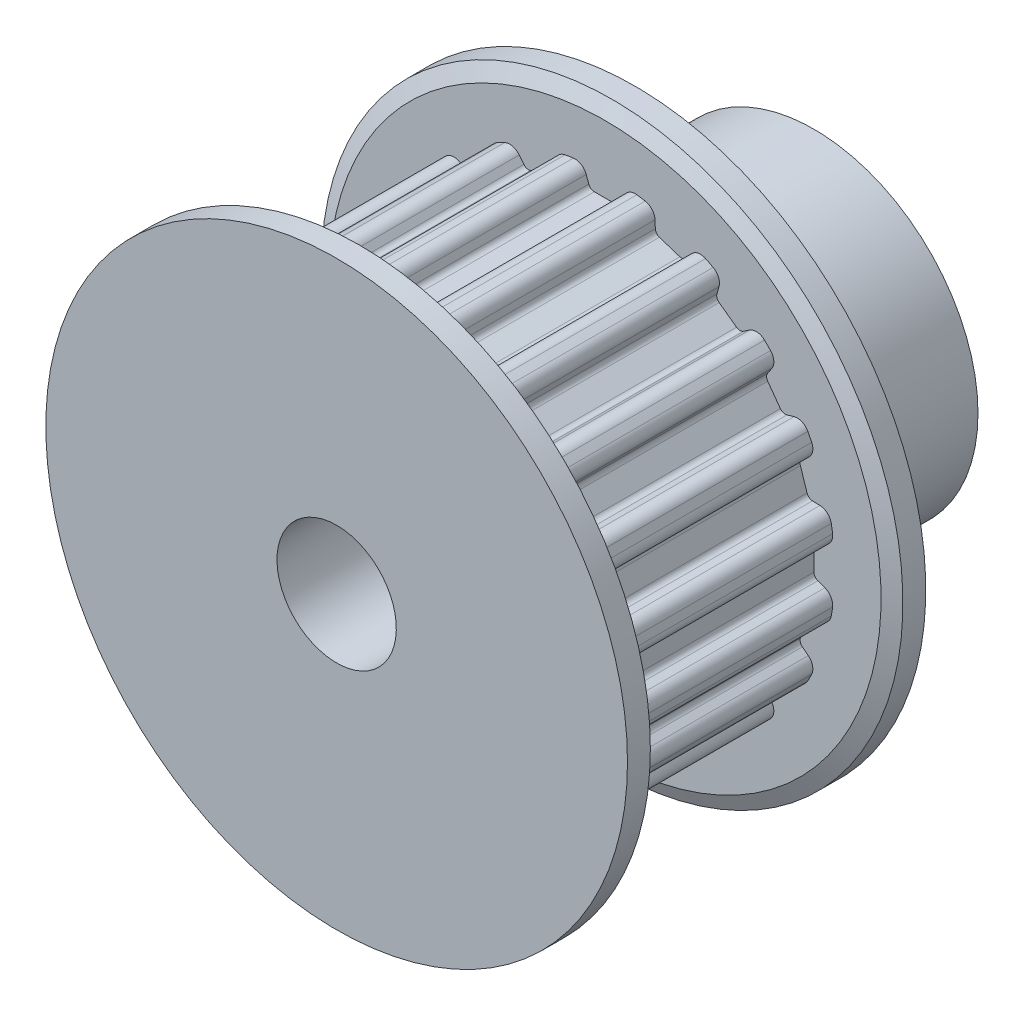
SolidWorks part; units mm, degrees
ref_plane "Front" through (0, 0, 0) normal (0, 0, 1) x (1, 0, 0)
ref_plane "Top" through (0, 0, 0) normal (0, 1, 0) x (1, 0, 0)
ref_plane "Right" through (0, 0, 0) normal (1, 0, 0) x (0, 0, -1)
sketch "support-front-body" plane through (0, 0, 0) normal (0, 0, 1) x (1, 0, 0)
  line L0 (0, 0) -> (0, 7.7) construction
  line L1 (0, 0) -> (0, -7.7) construction
  line L2 (0, 0) -> (7.7, 0) construction
  line L3 (0, 0) -> (-7.7, 0) construction
  circle A0 centre (0, 0) radius 7.7
  dimension "diam-outer" = 15.4
sketch "support-right-body" plane through (0, 0, 0) normal (1, 0, 0) x (0, 0, -1)
  line L0 (0, 0) -> (10, 0) construction
  line L1 (0, 7.7) -> (10, 7.7)
  line L2 (0, 7.7) -> (0, -7.7)
  line L3 (0, -7.7) -> (10, -7.7)
  line L4 (10, 7.7) -> (10, -7.7)
  dimension "length" = 10
sketch "support-right-chamfer" plane through (0, 0, 0) normal (1, 0, 0) x (0, 0, -1)
  line L0 (0, 0) -> (10, 0) construction
  line L1 (0, -7.7) -> (0, -6.7)
  line L2 (0, 7.7) -> (0, -7.7) construction
  line L4 (0, -6.7) -> (1, -7.7)
  line L5 (0, -7.7) -> (10, -7.7) construction
  line L7 (1, -7.7) -> (0, -7.7)
  line L9 (10, -7.7) -> (9, -7.7)
  line L11 (9, -7.7) -> (10, -6.7)
  line L12 (10, 7.7) -> (10, -7.7) construction
  line L14 (10, -6.7) -> (10, -7.7)
  dimension "height-chamfer-front" = 1
  dimension "angle-chamfer-front" = 45
  dimension "angle-chamfer-back" = 45
  dimension "height-chamfer-back" = 1
sketch "support-right-hub" plane through (0, 0, 0) normal (1, 0, 0) x (0, 0, -1)
  line L0 (16, 0) -> (10, 0) construction
  line L1 (10, 5.5) -> (16, 5.5)
  line L2 (10, 5.5) -> (10, -5.5)
  line L3 (10, -5.5) -> (16, -5.5)
  line L4 (16, 5.5) -> (16, -5.5)
  line L6 (0, 0) -> (10, 0) construction
  line L8 (0, 7.7) -> (0, -7.7) construction
  dimension "diam-hub" = 11
  dimension "length-hub" = 6
  dimension "dist-hub" = 10
sketch "support-right-bore" plane through (0, 0, 0) normal (1, 0, 0) x (0, 0, -1)
  line L0 (0, 7.7) -> (0, -7.7) construction
  line L1 (0, 2) -> (16, 2)
  line L2 (0, 2) -> (0, -2)
  line L3 (0, -2) -> (16, -2)
  line L4 (16, 2) -> (16, 0)
  line L5 (16, 0) -> (0, 0) construction
  line L6 (0, 0) -> (10, 0) construction
  line L7 (16, 0) -> (16, -2)
  line L8 (16, -2) -> (16, 2) construction
  dimension "diam-bore" = 4
  dimension "length-bore" = 16
  dimension "angle-bore-bottom" = 180
  dimension "angle-bore" = 90
sketch "support-stop-screw-hole" plane through (0, 0, 0) normal (1, 0, 0) x (0, 0, -1)
  line L1 (6.5667, 11) -> (9.4333, 11)
  line L2 (6.5667, 11) -> (6.5667, -1)
  line L3 (8, -1) -> (9.4333, -1)
  line L4 (9.4333, 11) -> (9.4333, -1)
  line L5 (8, -1) -> (8, 11) construction
  line L6 (8, -1) -> (6.5667, -1)
  line L7 (0, 0) -> (8, 0) construction
  line L8 (0, 7.7) -> (0, -7.7) construction
  dimension "diam-stop-screw-hole" = 2.8665
  dimension "dist-stop-screw-hole" = 8
  dimension "depth-stop-screw-hole" = 12
  dimension "angle-stop-screw-hole" = 180
  dimension "height-stop-screw-hole" = 11
sketch "support-front-keygroove" plane through (0, 0, 0) normal (0, 0, 1) x (1, 0, 0)
  line L0 (0, 0) -> (0, -2) construction
  line L1 (-1, 6) -> (1, 6)
  line L2 (-1, 6) -> (-1, 3.8)
  line L3 (-1, 3.8) -> (1, 3.8)
  line L4 (1, 6) -> (1, 3.8)
  line L5 (0, 0) -> (0, 2) construction
  circle A0 centre (0, 0) radius 2 construction
  dimension "width-keygroove" = 2
  dimension "dist-keygroove" = 8
  dimension "height-keygroove" = 2.2
sketch "support-front-tooth" plane through (0, 0, 0) normal (0, 0, 1) x (1, 0, 0)
  line L0 (0.5479, 7.1316) -> (0.6335, 7.3667)
  line L1 (0, 0) -> (0, 7.7) construction
  line L2 (-0.5479, 7.1316) -> (-0.6335, 7.3667)
  line L3 (-0.36, 7) -> (0.36, 7)
  line L4 (0, 7) -> (-1.0646, 7.626) construction
  line L5 (0, 7) -> (-0.5479, 7.1316) construction
  line L6 (0, 7.7) -> (0.5704, 7.6062) construction
  line L7 (0, 7.7) -> (2.4668, 7.2942) construction
  line L8 (0, 7.626) -> (0, 7) construction
  line L9 (1.0646, 7.626) -> (-1.0646, 7.626) construction
  line L10 (0, 7.626) -> (0, 8.2521) construction
  line L11 (0, 0) -> (1.2334, 7.4971) construction
  line L12 (1.4346, 7.5652) -> (1.6352, 8.1582)
  line L13 (1.6352, 8.1582) -> (3.6522, 7.4761)
  line L14 (3.6522, 7.4761) -> (3.4517, 6.883)
  line L15 (2.5836, 6.5157) -> (2.9601, 6.7755)
  line L16 (2.5836, 6.5157) -> (1.9016, 6.7464)
  line L17 (1.0646, 7.626) -> (1.0646, 8.2521)
  line L21 (-1.0646, 8.2521) -> (-1.0646, 7.626)
  line L22 (1.0646, 8.2521) -> (-1.0646, 8.2521)
  line L23 (1.9016, 6.7464) -> (1.76, 7.1814)
  line L24 (1.4346, 7.5652) -> (1.0646, 7.626) construction
  line L25 (-0.5479, 7.1316) -> (-0.5, 7) construction
  line L26 (-0.5, 7) -> (0.5, 7) construction
  line L27 (0.5, 7) -> (0.5479, 7.1316) construction
  line L28 (0.5704, 7.6062) -> (1.0093, 7.2299) construction
  arc A0 (-0.5479, 7.1316) -> (-0.36, 7) centre (-0.36, 7.2) ccw
  circle A1 centre (0, 0) radius 7.7 construction
  arc A2 (0.6335, 7.3667) -> (1.0646, 7.626) centre (1.0093, 7.2299) cw
  arc A3 (-0.6335, 7.3667) -> (-1.0646, 7.626) centre (-1.0093, 7.2299) ccw
  arc A4 (0.5479, 7.1316) -> (0.36, 7) centre (0.36, 7.2) cw
  circle A5 centre (0, 0) radius 7.7 construction
  arc A6 (1.76, 7.1814) -> (1.4346, 7.5652) centre (1.3601, 7.1722) ccw
  arc A7 (2.9601, 6.7755) -> (3.4517, 6.883) centre (3.2724, 6.5255) cw
  dimension "D3" = 0.4
  dimension "D2" = 40
  dimension "D1" = 0.2
  dimension "D4" = 1
  dimension "height-tooth" = 0.7
  dimension "pitch" = 2.5
sketch "support-right-flange" plane through (0, 0, 0) normal (1, 0, 0) x (0, 0, -1)
  line L0 (0, 4.85) -> (0, 8.1167)
  line L1 (10, 7.7) -> (10, -7.7) construction
  line L2 (0, 8.1167) -> (1, 8.1167) construction
  line L3 (1, 8.1167) -> (1, 9.75)
  line L4 (0, 9.75) -> (1, 9.75)
  line L5 (1, 8.1167) -> (1, 4.85)
  line L6 (1, 4.85) -> (0, 4.85)
  line L7 (5, 7.7) -> (5, 0) construction
  line L8 (0, 7.7) -> (10, 7.7) construction
  line L9 (0, 8.1167) -> (0, 9.75)
  line L10 (9, 4.85) -> (10, 4.85)
  line L11 (9, 8.1167) -> (9, 4.85)
  line L12 (10, 9.75) -> (9, 9.75)
  line L13 (9, 8.1167) -> (9, 9.75)
  line L14 (10, 8.1167) -> (10, 9.75)
  line L15 (10, 4.85) -> (10, 8.1167)
  line L16 (10, 0) -> (0, 0) construction
  line L17 (10, -4.85) -> (10, -8.1167)
  line L18 (10, -8.1167) -> (10, -9.75)
  line L19 (9, -8.1167) -> (9, -9.75)
  line L20 (10, -9.75) -> (9, -9.75)
  line L21 (9, -8.1167) -> (9, -4.85)
  line L22 (9, -4.85) -> (10, -4.85)
  line L23 (1, -4.85) -> (0, -4.85)
  line L24 (1, -8.1167) -> (1, -4.85)
  line L25 (0, -9.75) -> (1, -9.75)
  line L26 (1, -8.1167) -> (1, -9.75)
  line L27 (0, -8.1167) -> (0, -9.75)
  line L28 (0, -4.85) -> (0, -8.1167)
  line L29 (0, 0) -> (10, 0) construction
  line L30 (0, 8.1167) -> (1, 8.1167) construction
  line L31 (0.5, 4.85) -> (0.5, 6.4833) construction
  line L32 (0.5, 6.4833) -> (0.5, 8.1167) construction
  line L33 (0.5, 9.75) -> (0.5, 8.1167) construction
  line L34 (0, 7.7) -> (10, 7.7) construction
  dimension "angle-flange" = 180
  dimension "thickness-flange" = 1
  dimension "diam-flange-inner" = 9.7
  dimension "diam-flange-outer" = 19.5
  dimension "width-flange-inner" = 8
sketch "support-right-flange-profile" plane through (0, 0, 0) normal (1, 0, 0) x (0, 0, -1)
  line L0 (0.7668, 9.75) -> (1, 9.75)
  line L2 (1, 9.75) -> (1, 9.25)
  line L3 (1, 8.1167) -> (1, 4.85) construction
  line L4 (1, 9.25) -> (0.7668, 9.75)
  line L5 (0, 0) -> (10, 0) construction
  line L6 (5, 0) -> (5, 7.7) construction
  line L7 (9, 9.25) -> (9.2332, 9.75)
  line L8 (9, 9.75) -> (9, 9.25)
  line L9 (9.2332, 9.75) -> (9, 9.75)
  dimension "D1" = 25
  dimension "D2" = 0.5
ref_axis "ref-axis-center" through (0, 0, -10) along (0, 0, 1)
ref_plane "ref-plane-front" through (0, 0, 0) normal (0, 0, 1) x (1, 0, 0)
ref_plane "ref-plane-back" through (0, 0, -10) normal (0, 0, 1) x (1, 0, 0)
ref_plane "ref-plane-hub-front" through (0, 0, -10) normal (0, 0, 1) x (1, 0, 0)
ref_plane "ref-plane-hub-back" through (0, 0, -16) normal (0, 0, 1) x (1, 0, 0)
ref_plane "ref-plane-bore-front" through (0, 0, 0) normal (0, 0, 1) x (1, 0, 0)
ref_plane "ref-plane-bore-back" through (0, 0, -16) normal (0, 0, 1) x (1, 0, 0)
ref_plane "ref-plane-stop-screw-hole-top" through (0, 11, 0) normal (0, 1, 0) x (-1, 0, 0)
ref_axis "ref-axis-stop-screw-hole" through (0, 11, -8) along (0, -1, 0)
sketch "Sketch5" plane through (0, 0, 0) normal (1, 0, 0) x (0, 0, -1)
  line L0 (10, 7.7) -> (10, -7.7) construction
  line L1 (0, 7.7) -> (10, 7.7) construction
  line L2 (0, 7.7) -> (0, -7.7) construction
  line L3 (0, 0) -> (10, 0) construction
  line L4 (10, 7.7) -> (10, 0)
  line L5 (0, 7.7) -> (10, 7.7)
  line L6 (0, 7.7) -> (0, 0)
  line L7 (0, 0) -> (10, 0) construction
  line L8 (0, 0) -> (10, 0)
  dimension "D1" = 10
  dimension "D2" = 7.7
revolve "body" add sketch "Sketch5" angle 360 about L7
sketch "Sketch11" plane through (0, 0, 0) normal (1, 0, 0) x (0, 0, -1)
  line L0 (0, -7.7) -> (0, -6.7) construction
  line L3 (1, -7.7) -> (0, -7.7) construction
  line L5 (0, -6.7) -> (1, -7.7) construction
  line L8 (0, -7.7) -> (0, -6.7)
  line L9 (1, -7.7) -> (0, -7.7)
  line L10 (0, -6.7) -> (1, -7.7)
  line L11 (0, 0) -> (10, 0) construction
  line L12 (0, 0) -> (10, 0) construction
revolve "cut-chamfer-front" [suppressed] cut sketch "Sketch11" angle 360 about L12
sketch "Sketch13" plane through (0, 0, 0) normal (1, 0, 0) x (0, 0, -1)
  line L0 (0, 0) -> (10, 0) construction
  line L1 (10, -7.7) -> (9, -7.7) construction
  line L2 (10, -6.7) -> (10, -7.7) construction
  line L3 (9, -7.7) -> (10, -6.7) construction
  line L4 (0, 0) -> (10, 0) construction
  line L5 (10, -7.7) -> (9, -7.7)
  line L6 (10, -6.7) -> (10, -7.7)
  line L7 (9, -7.7) -> (10, -6.7)
revolve "cut-chamfer-back" [suppressed] cut sketch "Sketch13" angle 360 about L4
sketch "Sketch16" plane through (0, 0, 0) normal (1, 0, 0) x (0, 0, -1)
  line L0 (16, 5.5) -> (16, -5.5) construction
  line L1 (10, 5.5) -> (16, 5.5) construction
  line L2 (16, 0) -> (10, 0) construction
  line L3 (10, 5.5) -> (10, -5.5) construction
  line L4 (16, 5.5) -> (16, 0)
  line L5 (10, 5.5) -> (16, 5.5)
  line L6 (16, 0) -> (10, 0) construction
  line L7 (10, 5.5) -> (10, 0)
  line L8 (16, 0) -> (10, 0)
revolve "body-hub" add sketch "Sketch16" angle 360 about L6
sketch "Sketch17" plane through (0, 0, 0) normal (1, 0, 0) x (0, 0, -1)
  line L0 (16, 2) -> (16, 0) construction
  line L1 (16, 0) -> (0, 0) construction
  line L2 (0, 2) -> (16, 2) construction
  line L3 (0, 2) -> (0, -2) construction
  line L4 (16, 2) -> (16, 0)
  line L5 (16, 0) -> (0, 0) construction
  line L6 (0, 2) -> (16, 2)
  line L7 (0, 2) -> (0, 0)
  line L8 (16, 0) -> (0, 0)
  dimension "D1" = 2
revolve "body-bore" cut sketch "Sketch17" angle 360 about L5
sketch "Sketch19" plane through (0, 0, 0) normal (1, 0, 0) x (0, 0, -1)
  line L0 (6.5667, 11) -> (9.4333, 11) construction
  line L1 (8, -1) -> (8, 11) construction
  line L2 (9.4333, 11) -> (9.4333, -1) construction
  line L3 (8, -1) -> (9.4333, -1) construction
  line L4 (8, 11) -> (9.4333, 11)
  line L5 (8, -1) -> (8, 11) construction
  line L6 (9.4333, 11) -> (9.4333, -1)
  line L7 (8, -1) -> (9.4333, -1)
  line L8 (8, -1) -> (8, 11)
revolve "body-stop-screw-hole" [suppressed] cut sketch "Sketch19" angle 360 about L5
pattern_circular "pattern-stop-screw-hole" [suppressed] count 2 every 90 about axis through (0, 0, -10) along (0, 0, 1) reverse direction yes
sketch "Sketch21" plane through (0, 0, 0) normal (0, 0, 1) x (1, 0, 0)
  line L0 (-1, 6) -> (1, 6) construction
  line L1 (-1, 6) -> (-1, 3.8) construction
  line L2 (-1, 3.8) -> (1, 3.8) construction
  line L3 (1, 6) -> (1, 3.8) construction
  line L4 (-1, 6) -> (1, 6)
  line L5 (-1, 6) -> (-1, 3.8)
  line L6 (-1, 3.8) -> (1, 3.8)
  line L7 (1, 6) -> (1, 3.8)
extrude "cut-keygroove" [suppressed] cut sketch "Sketch21" against normal up to surface (17.5 mm away) up to plane "ref-plane-bore-back"
sketch "Sketch23" plane through (0, 0, 0) normal (0, 0, 1) x (1, 0, 0)
  line L0 (0.5479, 7.1316) -> (0.6335, 7.3667) construction
  line L1 (-0.5479, 7.1316) -> (-0.6335, 7.3667) construction
  line L2 (-1.0646, 8.2521) -> (-1.0646, 7.626) construction
  line L3 (1.0646, 8.2521) -> (-1.0646, 8.2521) construction
  line L4 (1.0646, 7.626) -> (1.0646, 8.2521) construction
  line L6 (0.5479, 7.1316) -> (0.6335, 7.3667)
  line L7 (-0.5479, 7.1316) -> (-0.6335, 7.3667)
  line L8 (-1.0646, 8.2521) -> (-1.0646, 7.626)
  line L9 (1.0646, 8.2521) -> (-1.0646, 8.2521)
  line L10 (1.0646, 7.626) -> (1.0646, 8.2521)
  line L11 (-0.36, 7) -> (0.36, 7) construction
  line L12 (-0.36, 7) -> (0.36, 7)
  arc A0 (0.36, 7) -> (0.5479, 7.1316) centre (0.36, 7.2) ccw construction
  arc A1 (-0.5479, 7.1316) -> (-0.36, 7) centre (-0.36, 7.2) ccw construction
  arc A2 (-0.6335, 7.3667) -> (-1.0646, 7.626) centre (-1.0093, 7.2299) ccw construction
  arc A3 (1.0646, 7.626) -> (0.6335, 7.3667) centre (1.0093, 7.2299) ccw construction
  arc A4 (0.36, 7) -> (0.5479, 7.1316) centre (0.36, 7.2) ccw
  arc A5 (-0.5479, 7.1316) -> (-0.36, 7) centre (-0.36, 7.2) ccw
  arc A6 (-0.6335, 7.3667) -> (-1.0646, 7.626) centre (-1.0093, 7.2299) ccw
  arc A7 (1.0646, 7.626) -> (0.6335, 7.3667) centre (1.0093, 7.2299) ccw
extrude "cut-tooth" cut sketch "Sketch23" against normal up to surface (10 mm away) up to plane "ref-plane-back"
pattern_circular "pattern-tooth" count 20 over 360 about axis through (0, 0, -10) along (0, 0, 1) of "cut-tooth"
sketch "Sketch25" plane through (0, 0, 0) normal (1, 0, 0) x (0, 0, -1)
  line L0 (0, 0) -> (10, 0) construction
  line L1 (1, 4.85) -> (0, 4.85) construction
  line L2 (1, 8.1167) -> (1, 4.85) construction
  line L4 (0, 9.75) -> (1, 9.75) construction
  line L5 (0, 8.1167) -> (0, 9.75) construction
  line L6 (0, 4.85) -> (0, 8.1167) construction
  line L7 (0, 0) -> (10, 0) construction
  line L8 (1, 4.85) -> (0, 4.85)
  line L9 (1, 8.1167) -> (1, 4.85)
  line L10 (0, 9.75) -> (1, 9.75)
  line L11 (1, 8.1167) -> (1, 9.75) construction
  line L12 (0, 8.1167) -> (0, 9.75)
  line L13 (0, 4.85) -> (0, 8.1167)
  line L14 (1, 8.1167) -> (1, 9.75)
revolve "body-flange-front" add sketch "Sketch25" angle 360 about L7
sketch "Sketch26" plane through (0, 0, 0) normal (1, 0, 0) x (0, 0, -1)
  line L0 (10, 0) -> (0, 0) construction
  line L1 (9, 4.85) -> (10, 4.85) construction
  line L2 (9, 8.1167) -> (9, 4.85) construction
  line L4 (10, 9.75) -> (9, 9.75) construction
  line L5 (10, 8.1167) -> (10, 9.75) construction
  line L6 (10, 4.85) -> (10, 8.1167) construction
  line L7 (10, 0) -> (0, 0) construction
  line L8 (9, 4.85) -> (10, 4.85)
  line L9 (9, 8.1167) -> (9, 4.85)
  line L10 (10, 9.75) -> (9, 9.75)
  line L11 (9, 8.1167) -> (9, 9.75) construction
  line L12 (10, 8.1167) -> (10, 9.75)
  line L13 (10, 4.85) -> (10, 8.1167)
  line L14 (9, 8.1167) -> (9, 9.75)
revolve "body-flange-back" add sketch "Sketch26" angle 360 about L7
sketch "Sketch28" plane through (0, 0, 0) normal (1, 0, 0) x (0, 0, -1)
  line L0 (1, 9.75) -> (1, 9.25) construction
  line L1 (0.7668, 9.75) -> (1, 9.75) construction
  line L2 (1, 9.25) -> (0.7668, 9.75) construction
  line L3 (1, 9.75) -> (1, 9.25)
  line L4 (0.7668, 9.75) -> (1, 9.75)
  line L5 (1, 9.25) -> (0.7668, 9.75)
  line L6 (10, 0) -> (0, 0) construction
  line L7 (10, 0) -> (0, 0) construction
revolve "body-flange-profile-front" cut sketch "Sketch28" angle 360 about L7
sketch "Sketch29" plane through (0, 0, 0) normal (1, 0, 0) x (0, 0, -1)
  line L0 (10, 0) -> (0, 0) construction
  line L1 (9, 9.75) -> (9, 9.25) construction
  line L2 (9.2332, 9.75) -> (9, 9.75) construction
  line L3 (9, 9.25) -> (9.2332, 9.75) construction
  line L4 (10, 0) -> (0, 0) construction
  line L5 (9, 9.75) -> (9, 9.25)
  line L6 (9.2332, 9.75) -> (9, 9.75)
  line L7 (9, 9.25) -> (9.2332, 9.75)
revolve "body-flange-profile-back" cut sketch "Sketch29" angle 360 about L4
sketch "support-right-cut-body" plane through (0, 0, 0) normal (1, 0, 0) x (0, 0, -1)
  line L0 (10, 7.7) -> (10, -7.7) construction
  line L1 (0, 7.7) -> (10, 7.7) construction
  line L2 (0, 7.7) -> (0, -7.7) construction
  line L3 (0, -7.7) -> (10, -7.7) construction
  line L4 (10, 7.7) -> (10, -7.7) construction
  line L5 (0, 7.7) -> (0, -7.7) construction
  line L6 (0, 7.7) -> (10, 7.7) construction
  line L7 (0, -7.7) -> (10, -7.7) construction
  line L8 (10, 0) -> (0, 0) construction
  line L9 (5, 7.7) -> (5, -7.7) construction
  line L10 (10, 58.5) -> (6.6667, 58.5)
  line L11 (10, 58.5) -> (10, -58.5)
  line L12 (10, -58.5) -> (6.6667, -58.5)
  line L13 (6.6667, 58.5) -> (6.6667, -58.5)
  line L14 (0, 58.5) -> (3.3333, 58.5)
  line L15 (0, 58.5) -> (0, -58.5)
  line L16 (0, -58.5) -> (3.3333, -58.5)
  line L17 (3.3333, 58.5) -> (3.3333, -58.5)
  line L18 (6.6667, 58.5) -> (3.3333, 58.5) construction
  line L19 (3.3333, -58.5) -> (5, -58.5) construction
  line L21 (10, 5.5) -> (6.6667, 5.5)
  line L23 (10, 5.5) -> (16, 5.5) construction
  line L24 (10, -5.5) -> (6.6667, -5.5)
  line L25 (0, 5.5) -> (3.3333, 5.5)
  line L26 (0, -5.5) -> (3.3333, -5.5)
  dimension "diam" = 117
sketch "support-front-cut-body" plane through (0, 0, 0) normal (0, 0, 1) x (1, 0, 0)
  line L0 (58.5, 0) -> (-58.5, 0) construction
  line L1 (0, 58.5) -> (0, 5.5) construction
  line L2 (0, 7.7) -> (0, -7.7) construction
  line L4 (0, 58.5) -> (-54.972, -20.0082) construction
  line L6 (0, -5.5) -> (0, -58.5) construction
  circle A0 centre (0, 32) radius 15.1998
  circle A1 centre (0, 0) radius 58.5 construction
  circle A2 centre (0, 0) radius 5.5 construction
  dimension "D1" = 35
sketch "Sketch31" plane through (0, 0, 0) normal (1, 0, 0) x (0, 0, -1)
  line L0 (0, 58.5) -> (0, -58.5) construction
  line L1 (0, 58.5) -> (3.3333, 58.5) construction
  line L2 (3.3333, 58.5) -> (3.3333, -58.5) construction
  line L3 (10, 58.5) -> (10, -58.5) construction
  line L4 (10, 58.5) -> (6.6667, 58.5) construction
  line L5 (6.6667, 58.5) -> (6.6667, -58.5) construction
  line L7 (0, 58.5) -> (0, 5.5)
  line L8 (0, 58.5) -> (3.3333, 58.5)
  line L9 (3.3333, 58.5) -> (3.3333, 5.5)
  line L10 (10, 58.5) -> (10, 5.5)
  line L11 (10, 58.5) -> (6.6667, 58.5)
  line L12 (6.6667, 58.5) -> (6.6667, 5.5)
  line L13 (10, 5.5) -> (6.6667, 5.5)
  line L14 (10, 5.5) -> (6.6667, 5.5) construction
  line L15 (3.3333, 5.5) -> (0, 5.5)
  line L16 (0, 0) -> (10, 0) construction
  line L17 (10, 0) -> (0, 0) construction
revolve "cut-body" [suppressed] cut sketch "Sketch31" angle 360 about L16
sketch "Sketch33" plane through (0, 0, 0) normal (0, 0, 1) x (1, 0, 0)
  circle A0 centre (0, 32) radius 15.1998 construction
  circle A1 centre (0, 32) radius 15.1998
extrude "cut-front-body" [suppressed] cut sketch "Sketch33" against normal through all
pattern_circular "pattern-cut-front-body" [suppressed] count 6 over 360 about axis through (0, 0, -10) along (0, 0, 1)
sketch "草图1" plane through (0, 0, -1) normal (0, 0, -1) x (-1, 0, 0)
  circle A0 centre (0, 0) radius 7.7
